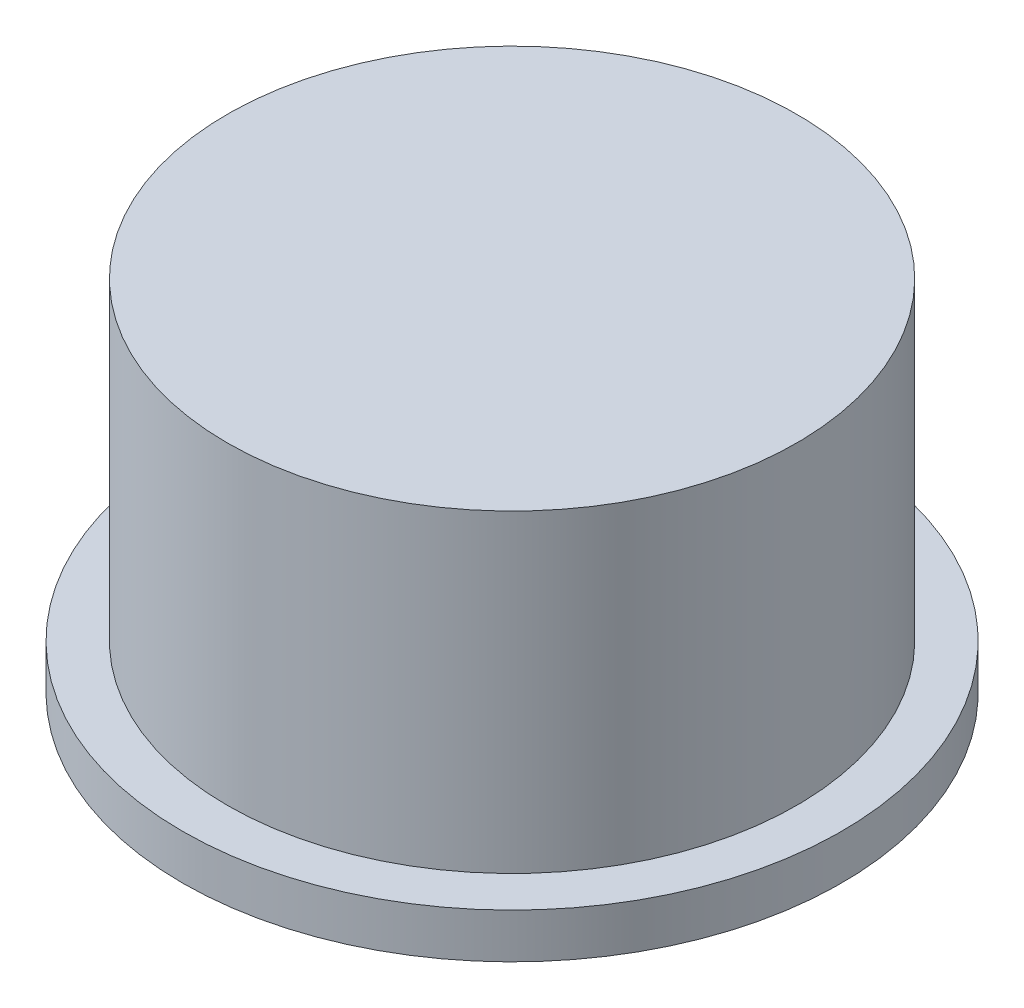
SolidWorks part; units mm, degrees
material "PVC 0.007 Plasticized"
ref_plane "Front Plane" through (0, 0, 0) normal (0, 0, 1) x (1, 0, 0)
ref_plane "Top Plane" through (0, 0, 0) normal (0, 1, 0) x (1, 0, 0)
ref_plane "Right Plane" through (0, 0, 0) normal (1, 0, 0) x (0, 0, -1)
sketch "Sketch1" plane through (0, 0, 0) normal (0, 1, 0) x (1, 0, 0)
  circle A0 centre (0, 0) radius 6.35
  circle A1 centre (0, 0) radius 7.35
  dimension "D1" = 12.7
  dimension "D2" = 14.7
extrude "Boss-Extrude1" add sketch "Sketch1" along normal blind 8 contours A0 region at (0, 0, 0)
extrude "Boss-Extrude2" add sketch "Sketch1<3>" along normal blind 1
sketch "Sketch1<3>" plane through (0, 0, 0) normal (0, 1, 0) x (1, 0, 0) same geometry as "Sketch1"
sketch "Sketch3" plane through (0, 0, 0) normal (0, 0, 1) x (1, 0, 0)
  line L1 (0, 0) -> (0, -2) construction
  line L2 (-3.5963, 0) -> (3.5963, 0)
  line L3 (-7.35, 0) -> (7.35, 0) construction
  arc A1 (3.5963, 0) -> (-3.5963, 0) centre (0, 2.2333) cw
  point P4 (0, -2)
  dimension "D2" = 4.2333
  dimension "D1" = 2
revolve "Revolve1" add sketch "Sketch3" angle 360 about L1 region at (-1.4043, -0.8188, 0)
